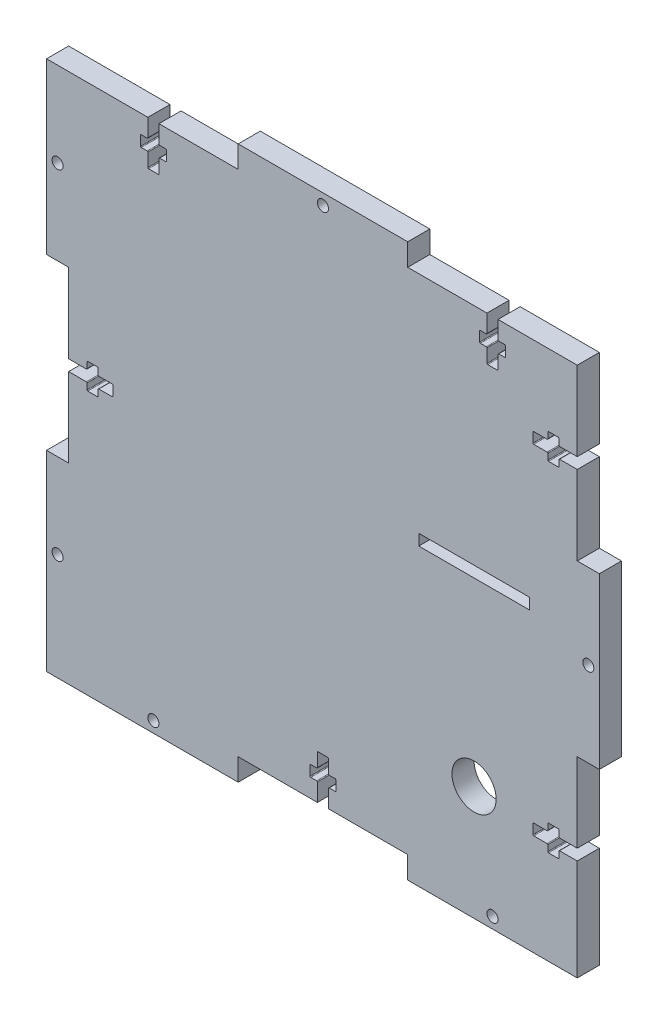
SolidWorks part; units mm, degrees
ref_plane "Front Plane" through (0, 0, 0) normal (0, 0, 1) x (1, 0, 0)
ref_plane "Top Plane" through (0, 0, 0) normal (0, 1, 0) x (1, 0, 0)
ref_plane "Right Plane" through (0, 0, 0) normal (1, 0, 0) x (0, 0, -1)
sketch "Sketch1" plane through (0, 0, 0) normal (0, 0, 1) x (1, 0, 0)
  line L0 (-69, 69) -> (-23, 69)
  line L5 (-75, -75) -> (75, -75) construction
  line L6 (-75, -75) -> (-75, 75) construction
  line L7 (-75, 75) -> (75, 75) construction
  line L8 (75, -75) -> (75, 75) construction
  line L9 (75, 23) -> (69, 23)
  line L10 (69, -23) -> (75, -23)
  line L11 (-69, -69) -> (69, -69) construction
  line L12 (-69, -69) -> (-69, 69) construction
  line L13 (-69, 69) -> (69, 69) construction
  line L14 (69, -69) -> (69, 69) construction
  line L15 (-69, -69) -> (69, 69) construction
  line L16 (69, -69) -> (69, -23)
  line L17 (-23, 69) -> (-23, 75)
  line L18 (-23, 75) -> (23, 75)
  line L19 (23, 75) -> (23, 69)
  line L20 (23, 69) -> (69, 69)
  line L21 (75, -23) -> (75, 23)
  line L22 (69, 23) -> (69, 69)
  line L23 (-75, 23) -> (-69, 23)
  line L24 (-69, 69) -> (-75, 69)
  line L25 (-75, 69) -> (-75, 23)
  line L26 (69, -69) -> (69, -75)
  line L27 (69, -75) -> (23, -75)
  line L28 (23, -75) -> (23, -69)
  line L29 (23, -69) -> (-23, -69)
  line L30 (-23, -69) -> (-23, -75)
  line L31 (-23, -75) -> (-69, -75)
  line L32 (-69, -75) -> (-69, -69) construction
  line L33 (-69, 23) -> (-69, -23)
  line L34 (-69, -23) -> (-75, -23)
  line L35 (-75, -23) -> (-75, -69)
  line L36 (-75, -69) -> (-69, -69) construction
  line L37 (-46, 69) -> (-46, -75) construction
  line L38 (-69, 69) -> (69, -69) construction
  line L39 (-75, -75) -> (-69, -75)
  line L40 (-75, -75) -> (-75, -69)
  point P0 (0, 0)
  point P6 (-7, -7)
  point P26 (0, -75)
  point P27 (-75, 0)
  dimension "D1" = 150
  dimension "D2" = 150
  dimension "D5" = 46
  dimension "D3" = 6
  dimension "D6" = 6
  dimension "D7" = 6
extrude "Box Side" add sketch "Sketch1" along normal blind 6
sketch "Sketch2" plane through (0, 0, 6) normal (0, 0, 1) x (1, 0, 0)
  line L0 (23, 72) -> (-23, 72) construction
  line L1 (23, 75) -> (23, 69) construction
  line L2 (-23, 69) -> (-23, 75) construction
  line L3 (-46, 69) -> (-46, -75) construction
  line L5 (0, 75) -> (0, 69) construction
  line L6 (-23, 75) -> (23, 75) construction
  line L7 (-69, 69) -> (69, 69) construction
  line L16 (-46, 69) -> (-46, -75) construction
  line L21 (0, -69) -> (0, 69) construction
  line L35 (-69, 69) -> (-23, 69) construction
  line L36 (-44.5, 69) -> (-44.5, 64.2)
  line L37 (-44.3, 64) -> (-42.7, 64)
  line L38 (-42.5, 63.8) -> (-42.5, 61.2)
  line L39 (-42.7, 61) -> (-44.3, 61)
  line L40 (-44.5, 60.8) -> (-44.5, 57.2)
  line L46 (-44.7, 57) -> (-47.3, 57)
  line L48 (-44.5, 69) -> (-47.5, 69)
  line L51 (-47.5, 60.8) -> (-47.5, 57.2)
  line L52 (-49.3, 61) -> (-47.7, 61)
  line L53 (-49.5, 63.8) -> (-49.5, 61.2)
  line L54 (-47.7, 64) -> (-49.3, 64)
  line L55 (-47.5, 69) -> (-47.5, 64.2)
  line L56 (47.5, 69) -> (47.5, 64.2)
  line L57 (47.7, 64) -> (49.3, 64)
  line L58 (49.5, 63.8) -> (49.5, 61.2)
  line L59 (49.3, 61) -> (47.7, 61)
  line L60 (47.5, 60.8) -> (47.5, 57.2)
  line L61 (44.5, 69) -> (47.5, 69)
  line L62 (44.7, 57) -> (47.3, 57)
  line L63 (44.5, 60.8) -> (44.5, 57.2)
  line L64 (42.7, 61) -> (44.3, 61)
  line L65 (42.5, 63.8) -> (42.5, 61.2)
  line L66 (44.3, 64) -> (42.7, 64)
  line L67 (44.5, 69) -> (44.5, 64.2)
  line L68 (-69, -69) -> (69, 69) construction
  line L69 (-69, -69) -> (69, 69) construction
  line L70 (75, 0) -> (69, 0) construction
  line L71 (72, 23) -> (72, -23) construction
  line L72 (69, 44.5) -> (64.2, 44.5)
  line L73 (64, 44.3) -> (64, 42.7)
  line L74 (63.8, 42.5) -> (61.2, 42.5)
  line L75 (61, 42.7) -> (61, 44.3)
  line L76 (60.8, 44.5) -> (57.2, 44.5)
  line L77 (57, 44.7) -> (57, 47.3)
  line L78 (69, 44.5) -> (69, 47.5)
  line L79 (60.8, 47.5) -> (57.2, 47.5)
  line L80 (61, 49.3) -> (61, 47.7)
  line L81 (63.8, 49.5) -> (61.2, 49.5)
  line L82 (64, 47.7) -> (64, 49.3)
  line L83 (69, 47.5) -> (64.2, 47.5)
  line L84 (69, -47.5) -> (64.2, -47.5)
  line L85 (64, -47.7) -> (64, -49.3)
  line L86 (63.8, -49.5) -> (61.2, -49.5)
  line L87 (61, -49.3) -> (61, -47.7)
  line L88 (60.8, -47.5) -> (57.2, -47.5)
  line L89 (69, -44.5) -> (69, -47.5)
  line L90 (57, -44.7) -> (57, -47.3)
  line L91 (60.8, -44.5) -> (57.2, -44.5)
  line L92 (61, -42.7) -> (61, -44.3)
  line L93 (63.8, -42.5) -> (61.2, -42.5)
  line L94 (64, -44.3) -> (64, -42.7)
  line L95 (69, -44.5) -> (64.2, -44.5)
  line L120 (-69, 69) -> (69, -69) construction
  line L121 (-69, 69) -> (69, -69) construction
  line L122 (-1.5, -69) -> (1.5, -69)
  line L123 (-23, -69) -> (23, -69) construction
  line L124 (1.5, -69) -> (1.5, -64.2)
  line L125 (1.7, -64) -> (3.3, -64)
  line L126 (3.5, -63.8) -> (3.5, -61.2)
  line L127 (3.3, -61) -> (1.7, -61)
  line L128 (1.5, -60.8) -> (1.5, -57.2)
  line L129 (1.3, -57) -> (-1.3, -57)
  line L130 (-1.5, -60.8) -> (-1.5, -57.2)
  line L131 (-3.3, -61) -> (-1.7, -61)
  line L132 (-3.5, -63.8) -> (-3.5, -61.2)
  line L133 (-1.7, -64) -> (-3.3, -64)
  line L134 (-1.5, -69) -> (-1.5, -64.2)
  line L135 (-69, -1.5) -> (-64.2, -1.5)
  line L136 (-64, -1.7) -> (-64, -3.3)
  line L137 (-63.8, -3.5) -> (-61.2, -3.5)
  line L138 (-61, -3.3) -> (-61, -1.7)
  line L139 (-60.8, -1.5) -> (-57.2, -1.5)
  line L140 (-57, 1.3) -> (-57, -1.3)
  line L141 (-60.8, 1.5) -> (-57.2, 1.5)
  line L142 (-61, 3.3) -> (-61, 1.7)
  line L143 (-63.8, 3.5) -> (-61.2, 3.5)
  line L144 (-64, 1.7) -> (-64, 3.3)
  line L145 (-69, 1.5) -> (-64.2, 1.5)
  line L146 (-69, -1.5) -> (-69, 1.5)
  line L147 (-69, -72) -> (-23, -72) construction
  line L148 (-23, 69) -> (-75, 69) construction
  line L149 (-23, -75) -> (-23, -69) construction
  line L150 (-69, -69) -> (-69, -75) construction
  line L151 (-75, -75) -> (-23, -75) construction
  circle A0 centre (0, 72) radius 1.5
  arc A1 (-44.5, 57.2) -> (-44.7, 57) centre (-44.7, 57.2) cw
  arc A2 (-44.3, 61) -> (-44.5, 60.8) centre (-44.3, 60.8) ccw
  arc A3 (-42.5, 61.2) -> (-42.7, 61) centre (-42.7, 61.2) cw
  arc A4 (-42.7, 64) -> (-42.5, 63.8) centre (-42.7, 63.8) cw
  arc A5 (-44.5, 64.2) -> (-44.3, 64) centre (-44.3, 64.2) ccw
  arc A6 (-47.5, 64.2) -> (-47.7, 64) centre (-47.7, 64.2) cw
  arc A7 (-49.3, 64) -> (-49.5, 63.8) centre (-49.3, 63.8) ccw
  arc A8 (-49.5, 61.2) -> (-49.3, 61) centre (-49.3, 61.2) ccw
  arc A9 (-47.7, 61) -> (-47.5, 60.8) centre (-47.7, 60.8) cw
  arc A10 (-47.5, 57.2) -> (-47.3, 57) centre (-47.3, 57.2) ccw
  arc A11 (47.5, 57.2) -> (47.3, 57) centre (47.3, 57.2) cw
  arc A12 (47.7, 61) -> (47.5, 60.8) centre (47.7, 60.8) ccw
  arc A13 (49.5, 61.2) -> (49.3, 61) centre (49.3, 61.2) cw
  arc A14 (49.3, 64) -> (49.5, 63.8) centre (49.3, 63.8) cw
  arc A15 (47.5, 64.2) -> (47.7, 64) centre (47.7, 64.2) ccw
  arc A16 (44.5, 64.2) -> (44.3, 64) centre (44.3, 64.2) cw
  arc A17 (42.7, 64) -> (42.5, 63.8) centre (42.7, 63.8) ccw
  arc A18 (42.5, 61.2) -> (42.7, 61) centre (42.7, 61.2) ccw
  arc A19 (44.3, 61) -> (44.5, 60.8) centre (44.3, 60.8) cw
  arc A20 (44.5, 57.2) -> (44.7, 57) centre (44.7, 57.2) ccw
  arc A21 (57.2, 44.5) -> (57, 44.7) centre (57.2, 44.7) cw
  arc A22 (61, 44.3) -> (60.8, 44.5) centre (60.8, 44.3) ccw
  arc A23 (61.2, 42.5) -> (61, 42.7) centre (61.2, 42.7) cw
  arc A24 (64, 42.7) -> (63.8, 42.5) centre (63.8, 42.7) cw
  arc A25 (64.2, 44.5) -> (64, 44.3) centre (64.2, 44.3) ccw
  arc A26 (64.2, 47.5) -> (64, 47.7) centre (64.2, 47.7) cw
  arc A27 (64, 49.3) -> (63.8, 49.5) centre (63.8, 49.3) ccw
  arc A28 (61.2, 49.5) -> (61, 49.3) centre (61.2, 49.3) ccw
  arc A29 (61, 47.7) -> (60.8, 47.5) centre (60.8, 47.7) cw
  arc A30 (57.2, 47.5) -> (57, 47.3) centre (57.2, 47.3) ccw
  arc A31 (57.2, -47.5) -> (57, -47.3) centre (57.2, -47.3) cw
  arc A32 (61, -47.7) -> (60.8, -47.5) centre (60.8, -47.7) ccw
  arc A33 (61.2, -49.5) -> (61, -49.3) centre (61.2, -49.3) cw
  arc A34 (64, -49.3) -> (63.8, -49.5) centre (63.8, -49.3) cw
  arc A35 (64.2, -47.5) -> (64, -47.7) centre (64.2, -47.7) ccw
  arc A36 (64.2, -44.5) -> (64, -44.3) centre (64.2, -44.3) cw
  arc A37 (64, -42.7) -> (63.8, -42.5) centre (63.8, -42.7) ccw
  arc A38 (61.2, -42.5) -> (61, -42.7) centre (61.2, -42.7) ccw
  arc A39 (61, -44.3) -> (60.8, -44.5) centre (60.8, -44.3) cw
  arc A40 (57.2, -44.5) -> (57, -44.7) centre (57.2, -44.7) ccw
  circle A41 centre (72, 0) radius 1.5
  arc A62 (1.5, -57.2) -> (1.3, -57) centre (1.3, -57.2) ccw
  arc A63 (1.7, -61) -> (1.5, -60.8) centre (1.7, -60.8) cw
  arc A64 (3.5, -61.2) -> (3.3, -61) centre (3.3, -61.2) ccw
  arc A65 (3.3, -64) -> (3.5, -63.8) centre (3.3, -63.8) ccw
  arc A66 (1.5, -64.2) -> (1.7, -64) centre (1.7, -64.2) cw
  arc A67 (-1.5, -64.2) -> (-1.7, -64) centre (-1.7, -64.2) ccw
  arc A68 (-3.3, -64) -> (-3.5, -63.8) centre (-3.3, -63.8) cw
  arc A69 (-3.5, -61.2) -> (-3.3, -61) centre (-3.3, -61.2) cw
  arc A70 (-1.7, -61) -> (-1.5, -60.8) centre (-1.7, -60.8) ccw
  arc A71 (-1.5, -57.2) -> (-1.3, -57) centre (-1.3, -57.2) cw
  arc A72 (-57.2, -1.5) -> (-57, -1.3) centre (-57.2, -1.3) ccw
  arc A73 (-61, -1.7) -> (-60.8, -1.5) centre (-60.8, -1.7) cw
  arc A74 (-61.2, -3.5) -> (-61, -3.3) centre (-61.2, -3.3) ccw
  arc A75 (-64, -3.3) -> (-63.8, -3.5) centre (-63.8, -3.3) ccw
  arc A76 (-64.2, -1.5) -> (-64, -1.7) centre (-64.2, -1.7) cw
  arc A77 (-64.2, 1.5) -> (-64, 1.7) centre (-64.2, 1.7) ccw
  arc A78 (-64, 3.3) -> (-63.8, 3.5) centre (-63.8, 3.3) cw
  arc A79 (-61.2, 3.5) -> (-61, 3.3) centre (-61.2, 3.3) cw
  arc A80 (-61, 1.7) -> (-60.8, 1.5) centre (-60.8, 1.7) ccw
  arc A81 (-57.2, 1.5) -> (-57, 1.3) centre (-57.2, 1.3) cw
  circle A82 centre (-46, -72) radius 1.5
  circle A83 centre (46, -72) radius 1.5
  circle A84 centre (-72, 46) radius 1.5
  circle A85 centre (-72, -46) radius 1.5
  point P6 (0, 72)
  point P38 (0, 0)
  point P56 (-46, 57)
  point P88 (46, 57)
  point P161 (57, 46)
  point P162 (57, -46)
  point P198 (0, -57)
  point P231 (-57, 0)
  point P234 (-42.5, 62.5)
  dimension "D1" = 3
  dimension "D2" = 0.2
  dimension "D8" = 0.2
  dimension "D14" = 3
  dimension "D4" = 3
  dimension "D7" = 1.5
  dimension "D10" = 3
  dimension "D12" = 1.5
  dimension "D9" = 12
  dimension "D11" = 5
  dimension "D13" = 7
  dimension "D3" = 12
  dimension "D5" = 7
  dimension "D6" = 5
extrude "Screw Cut-outs" cut sketch "Sketch2" against normal through all
sketch "Bearing Hole" plane through (0, 0, 6) normal (0, 0, 1) x (1, 0, 0)
  line L0 (23, -69) -> (50023, -69) construction
  line L4 (41, -41) -> (50041, -41) construction
  line L5 (41.5774, -47) -> (50041.5774, -47) construction
  line L8 (44, -52) -> (44, -50052) construction
  line L9 (69, -75) -> (69, -47.5) construction
  circle A0 centre (41, -44) radius 3 construction
  circle A1 centre (41, -54) radius 15 construction
  circle A2 centre (41, -44) radius 6
  dimension "D2" = 6
  dimension "D4" = 30
  dimension "D5" = 12
  dimension "D1" = 7
  dimension "D3" = 25
extrude "Shaft Hole" cut sketch "Bearing Hole" against normal through all
sketch "Sketch4" plane through (0, 0, 0) normal (0, 0, -1) x (-1, 0, 0)
  line L0 (-72, 1.5) -> (49928, 1.5) construction
  line L1 (-56, 8) -> (-26, 8)
  line L2 (-56, 8) -> (-56, 5)
  line L3 (-56, 5) -> (-26, 5)
  line L4 (-26, 8) -> (-26, 5)
  line L5 (-75, -23) -> (-75, 23) construction
  circle A1 centre (-72, 0) radius 1.5 construction
  dimension "D1" = 3.5
  dimension "D2" = 30
  dimension "D3" = 3
  dimension "D4" = 19
extrude "Grooves" cut sketch "Sketch4" against normal up to surface (6 mm away) up to face at (47, -44, 6)
equation "\"filletRadius\"=0.2"
equation "\"D8@Sketch2\"=\"filletRadius\""
equation "\"D2@Sketch2\"=\"filletRadius\""
equation "\"fingerWidth\"= 46"
equation "\"D5@Sketch1\"=\"fingerWidth\""
equation "\"wallThickness\"= 6"
equation "\"D3@Sketch1\" = \"wallThickness\""
equation "\"D6@Sketch1\" = \"wallThickness\""
equation "\"D7@Sketch1\" = \"wallThickness\""
equation "\"D1@Box Side\" = \"wallThickness\""
equation "\"M3\"= 3"
equation "\"D14@Sketch2\"=\"M3\""
equation "\"D1@Sketch2\"=\"M3\""
equation "\"D12@Sketch2\"=\"M3\"/2"
equation "\"nutThickness\"=3"
equation "\"D10@Sketch2\" = \"nutThickness\""
equation "\"boltLength\"= 12"
equation "\"D9@Sketch2\" = \"boltLength\""
equation "\"distanceToNut\"= 5"
equation "\"D11@Sketch2\" = \"distanceToNut\""
equation "\"D13@Sketch2\" = \"nutWidth\""
equation "\"D7@Sketch2\"=\"M3\"/2"
equation "\"D4@Sketch2\" = \"nutThickness\""
equation "\"D3@Sketch2\" = \"boltLength\""
equation "\"D5@Sketch2\" = \"nutWidth\""
equation "\"D6@Sketch2\" = \"distanceToNut\""
equation "\"sideLength\"=150"
equation "\"D1@Sketch1\"=\"sideLength\""
equation "\"D2@Sketch1\"=\"sideLength\""
equation "\"nutWidth\"=7"
